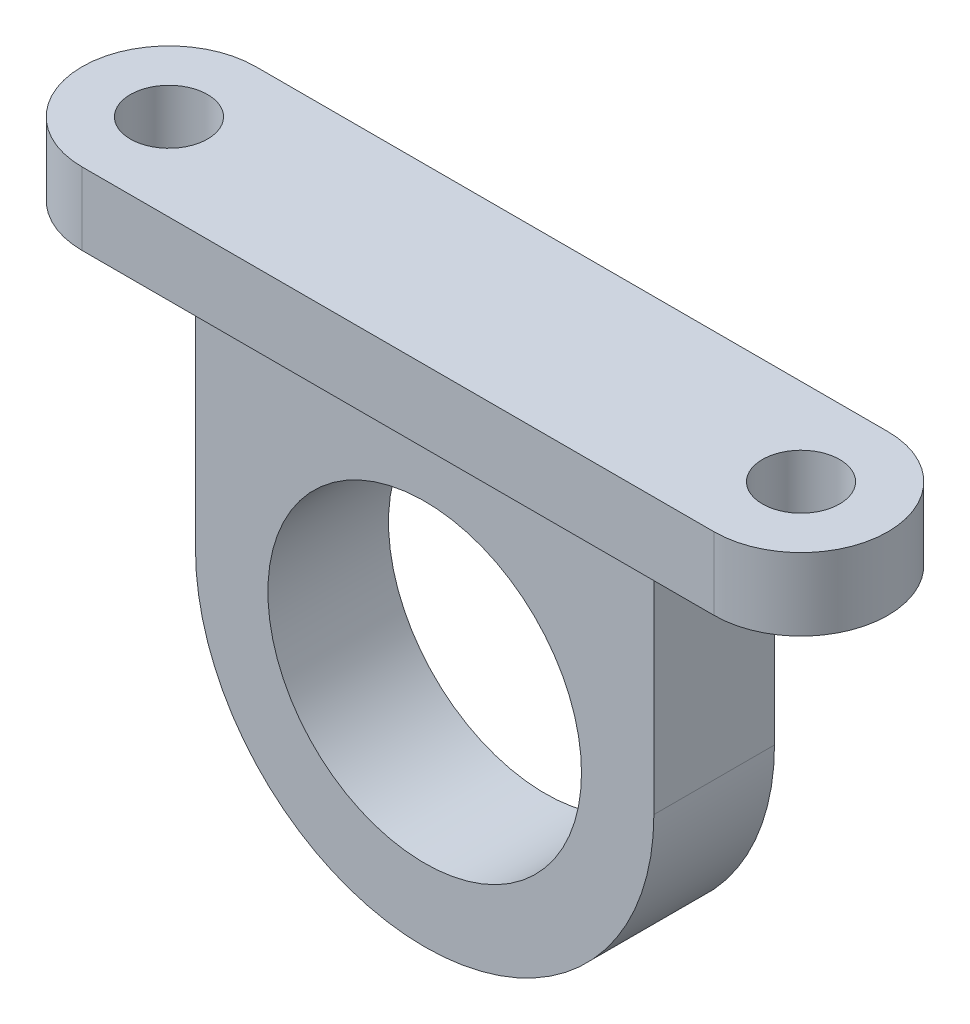
SolidWorks part; units mm, degrees
material "Plain Carbon Steel"
ref_plane "Front Plane" through (0, 0, 0) normal (0, 0, 1) x (1, 0, 0)
ref_plane "Top Plane" through (0, 0, 0) normal (0, 1, 0) x (1, 0, 0)
ref_plane "Right Plane" through (0, 0, 0) normal (1, 0, 0) x (0, 0, -1)
sketch "Sketch1" plane through (0, 0, 0) normal (0, 0, 1) x (1, 0, 0)
  line L0 (-9.5, 0) -> (-9.5, 9.5)
  line L1 (9.5, 0) -> (9.5, 9.5)
  line L2 (-9.5, 9.5) -> (9.5, 9.5)
  circle A0 centre (0, 0) radius 6.5
  arc A1 (-9.5, 0) -> (9.5, 0) centre (0, 0) ccw
  circle A2 centre (0, 0) radius 9.5 construction
  dimension "D1" = 13
  dimension "D3" = 9.5
  dimension "D2" = 3
extrude "Boss-Extrude1" add sketch "Sketch1" along normal blind 5
sketch "Sketch2" plane through (0, 9.5, 0) normal (0, 1, 0) x (1, 0, 0)
  line L4 (0, 1.1) -> (0, 0) construction
  line L5 (0, 0) -> (0, -5) construction
  line L15 (13.1, 1.1) -> (-13.1, 1.1)
  line L16 (9.5, -5) -> (-9.5, -5) construction
  line L22 (0, -5) -> (0, -6.1) construction
  line L23 (-9.5, -5) -> (-9.5, 0) construction
  line L31 (-13.1, -6.1) -> (13.1, -6.1)
  circle A0 centre (-13.1, -2.5) radius 1.6
  arc A1 (-13.1, 1.1) -> (-13.1, -6.1) centre (-13.1, -2.5) ccw
  arc A2 (13.1, 1.1) -> (13.1, -6.1) centre (13.1, -2.5) cw
  circle A3 centre (13.1, -2.5) radius 1.6
  point P1 (-12.413, -6.1)
  point P11 (-11.1203, 0.8034)
  line M3 (9.5, 0) -> (-9.5, 0)
  line M4 (-9.5, 0) -> (-9.5, -5)
  line M5 (-9.5, -5) -> (9.5, -5)
  line M6 (9.5, -5) -> (9.5, 0)
  dimension "D2" = 3.2
  dimension "D1" = 3.6
  dimension "D3" = 3.6
extrude "Boss-Extrude2" add sketch "Sketch2" along normal blind 3 contours M6 M3 M4 M5 | M4 | M6 region at (16.3583, 9.5, 2.5) region at (0, 9.5, 2.5)
